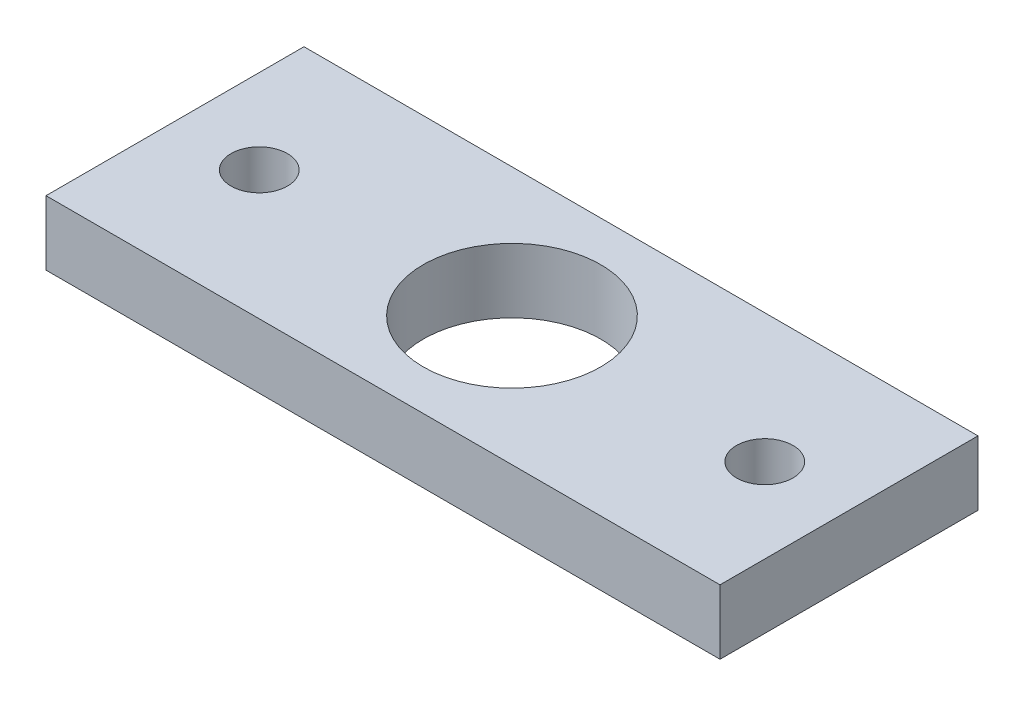
SolidWorks part; units mm, degrees
ref_plane "Front Plane" through (0, 0, 0) normal (0, 0, 1) x (1, 0, 0)
ref_plane "Top Plane" through (0, 0, 0) normal (0, 1, 0) x (1, 0, 0)
ref_plane "Right Plane" through (0, 0, 0) normal (1, 0, 0) x (0, 0, -1)
sketch "Sketch1" plane through (0, 0, 0) normal (0, 1, 0) x (1, 0, 0)
  line L0 (0, 14.9855) -> (0, -14.5762) construction
  line L1 (-20.9, -8) -> (20.9, -8)
  line L2 (-20.9, -8) -> (-20.9, 8)
  line L3 (-20.9, 8) -> (20.9, 8)
  line L4 (20.9, -8) -> (20.9, 8)
  line L5 (-20.4683, 0) -> (27.4527, 0) construction
  circle A0 centre (-15.675, 0) radius 1.75
  circle A1 centre (15.675, 0) radius 1.75
  circle A2 centre (0, 0) radius 9.5
  circle A3 centre (0, 0) radius 4.5
  circle A4 centre (0, 0) radius 5.5
  point P0 (0, 0)
  dimension "D3" = 19
  dimension "D4" = 3.5
  dimension "D6" = 9
  dimension "D7" = 11
  dimension "D1" = 41.8
  dimension "D2" = 16
  dimension "D5" = 15.675
extrude "Boss-Extrude1" add sketch "Sketch1" along normal blind 4 contours L1 A2 L3 | A2 L1 L4 L3 A1 | A2 L3 L2 L1 A0 region at (-20.6753, 0, 0) region at (-9.2516, 0, 0) region at (8.5315, 0, 4.6673)
equation "\"Bearing Outer Radius\"= 19"
equation "\"Plate Length\" = \"Bearing Outer Radius\" * 2.2"
equation "\"Plate Width\" = \"Bearing Outer Radius\" - 3"
equation "\"Bearing Inner Radius\"= 9"
equation "\"D2@Sketch1\"=\"Plate Width\""
equation "\"D3@Sketch1\"=\"Bearing Outer Radius\""
equation "\"D1@Sketch1\"=\"Plate Length\""
equation "\"D6@Sketch1\"=\"Bearing Inner Radius\""
equation "\"D7@Sketch1\"=\"Bearing Inner Radius\" + 2"
equation "\"D5@Sketch1\"=\"Plate Length\" * 3/8"
